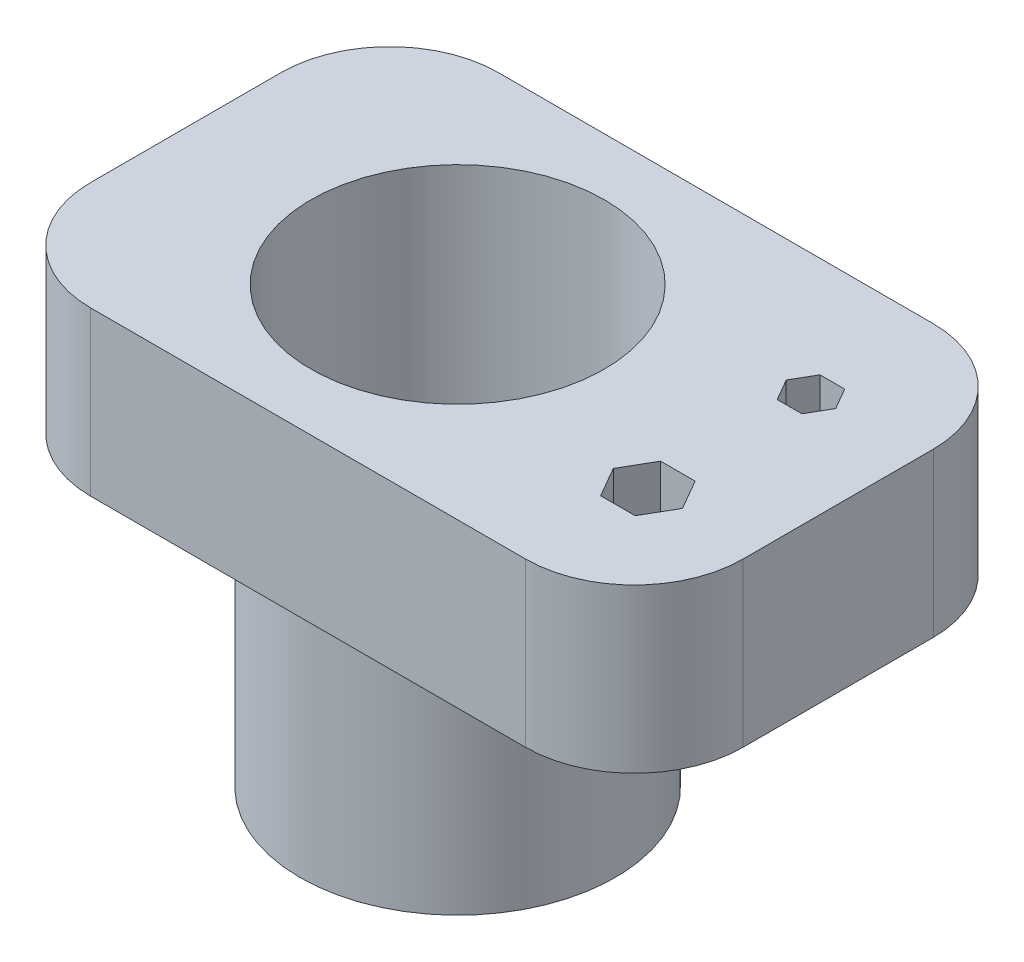
SolidWorks part; units mm, degrees
ref_plane "Front Plane" through (0, 0, 0) normal (0, 0, 1) x (1, 0, 0)
ref_plane "Top Plane" through (0, 0, 0) normal (0, 1, 0) x (1, 0, 0)
ref_plane "Right Plane" through (0, 0, 0) normal (1, 0, 0) x (0, 0, -1)
sketch "Sketch1" plane through (0, 0, 0) normal (0, 1, 0) x (1, 0, 0)
  circle A0 centre (0, 0) radius 3.683
  circle A1 centre (0, 0) radius 3.429
  dimension "D1" = 7.366
  dimension "D2" = 6.858
extrude "Boss-Extrude1" add sketch "Sketch1" along normal blind 6.35
fillet "Fillet1" radius 2.54 1 edges at (0, 0, 3.429)
sketch "Sketch2" plane through (0, 6.35, 0) normal (0, 1, 0) x (1, 0, 0)
  line L0 (-55, 0) -> (55, 0) construction
  line L1 (8.89, 4.7625) -> (-6.35, 4.7625)
  line L2 (8.89, 4.7625) -> (8.89, -4.7625)
  line L3 (8.89, -4.7625) -> (-6.35, -4.7625)
  line L4 (-6.35, 4.7625) -> (-6.35, -4.7625)
  line L5 (8.89, 4.7625) -> (-6.35, -4.7625) construction
  line L6 (8.89, -4.7625) -> (-6.35, 4.7625) construction
  line L7 (0, -55) -> (0, 55) construction
  point P0 (1.27, 0)
  dimension "D1" = 9.525
  dimension "D2" = 15.24
  dimension "D3" = 1.27
extrude "Boss-Extrude2" add sketch "Sketch2" along normal blind 3.81
sketch "Sketch3" plane through (0, 6.35, 0) normal (0, -1, 0) x (1, 0, 0)
  circle A0 centre (0, 0) radius 3.429 construction
  circle A1 centre (0, 0) radius 3.429
extrude "Cut-Extrude1" cut sketch "Sketch3" against normal through all
sketch "Sketch4" plane through (0, 10.16, 0) normal (0, 1, 0) x (1, 0, 0)
  line L1 (6.0613, 1.405) -> (6.6387, 1.405)
  line L2 (6.6387, 1.405) -> (6.9274, 1.905)
  line L3 (6.9274, 1.905) -> (6.6387, 2.405)
  line L4 (6.6387, 2.405) -> (6.0613, 2.405)
  line L5 (6.0613, 2.405) -> (5.7726, 1.905)
  line L6 (5.7726, 1.905) -> (6.0613, 1.405)
  line L7 (8.89, -4.7625) -> (8.89, 4.7625) construction
  line L8 (-5.588, 0) -> (5.588, 0) construction
  line L10 (7.1583, -1.905) -> (6.7541, -1.205)
  line L11 (6.7541, -1.205) -> (5.9459, -1.205)
  line L12 (5.9459, -1.205) -> (5.5417, -1.905)
  line L13 (5.5417, -1.905) -> (5.9459, -2.605)
  line L14 (5.9459, -2.605) -> (6.7541, -2.605)
  line L15 (6.7541, -2.605) -> (7.1583, -1.905)
  circle A0 centre (6.35, 1.905) radius 0.5 construction
  circle A1 centre (6.35, -1.905) radius 0.7 construction
  point P1 (0, 0)
  dimension "D1" = 1
  dimension "D2" = 2.54
  dimension "D3" = 1.905
  dimension "D4" = 1.4
  dimension "D5" = 1.905
extrude "Cut-Extrude2" cut sketch "Sketch4" against normal blind 3.81
fillet "Fillet2" radius 2.54 4 edges at (-6.35, 8.255, 4.7625) (-6.35, 8.255, -4.7625) (8.89, 8.255, -4.7625) (8.89, 8.255, 4.7625)
